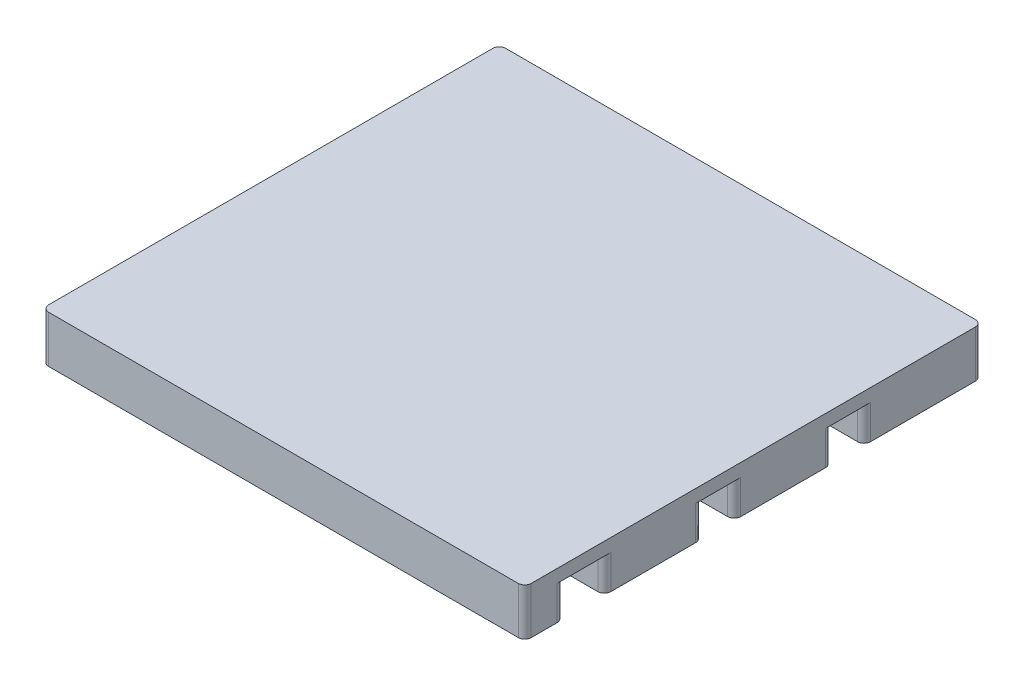
SolidWorks part; units mm, degrees
ref_plane "Front Plane" through (0, 0, 0) normal (0, 0, 1) x (1, 0, 0)
ref_plane "Top Plane" through (0, 0, 0) normal (0, 1, 0) x (1, 0, 0)
ref_plane "Right Plane" through (0, 0, 0) normal (1, 0, 0) x (0, 0, -1)
sketch "Sketch3" plane through (0, 0, 0) normal (0, 1, 0) x (1, 0, 0)
  line L1 (0, 0) -> (149, 0)
  line L2 (0, 0) -> (0, -141.12)
  line L3 (0, -141.12) -> (149, -141.12)
  line L4 (149, 0) -> (149, -141.12)
  dimension "D1" = 141.12
  dimension "D2" = 149
extrude "Boss-Extrude1" add sketch "Sketch3" along normal blind 4
sketch "Sketch5" plane through (0, 4, 0) normal (0, 1, 0) x (1, 0, 0)
  line L0 (0, 0) -> (0, -141.12) construction
  line L1 (149, 0) -> (82, 0)
  line L2 (149, 0) -> (149, -36.35)
  line L3 (149, -36.35) -> (82, -36.35)
  line L4 (82, 0) -> (82, -36.35)
  line L5 (0, -8.7) -> (67, -8.7)
  line L6 (0, -8.7) -> (0, -38.9)
  line L7 (0, -38.9) -> (67, -38.9)
  line L8 (67, -8.7) -> (67, -38.9)
  line L9 (149, 0) -> (0, 0) construction
  line L10 (149, -141.12) -> (149, 0) construction
  line L11 (0, -48.8) -> (67, -48.8)
  line L12 (0, -48.8) -> (0, -79)
  line L13 (0, -79) -> (67, -79)
  line L14 (67, -48.8) -> (67, -79)
  line L15 (0, -88.9) -> (67, -88.9)
  line L16 (0, -88.9) -> (0, -119.1)
  line L17 (0, -119.1) -> (67, -119.1)
  line L18 (67, -88.9) -> (67, -119.1)
  line L19 (149, -46.25) -> (82, -46.25)
  line L20 (149, -46.25) -> (149, -76.45)
  line L21 (149, -76.45) -> (82, -76.45)
  line L22 (82, -46.25) -> (82, -76.45)
  line L23 (13, -8.7) -> (13, -21.7) construction
  line L24 (149, -86.35) -> (82, -86.35)
  line L25 (149, -86.35) -> (149, -116.55)
  line L26 (149, -116.55) -> (82, -116.55)
  line L27 (82, -86.35) -> (82, -116.55)
  line L28 (13, -21.7) -> (13, -27.9) construction
  line L29 (13, -27.9) -> (13, -38.9) construction
  line L30 (13, -21.7) -> (41, -21.7)
  line L31 (13, -27.9) -> (41, -27.9)
  line L32 (13, -48.8) -> (13, -61.8) construction
  line L33 (13, -61.8) -> (13, -68) construction
  line L34 (13, -68) -> (13, -79) construction
  line L35 (13, -61.8) -> (41, -61.8)
  line L36 (13, -68) -> (41, -68)
  line L37 (97, -36.35) -> (97, -25.35) construction
  line L38 (97, -25.35) -> (97, -19.15) construction
  line L39 (97, -19.15) -> (97, 0) construction
  line L40 (97, -19.15) -> (125, -19.15)
  line L41 (97, -25.35) -> (125, -25.35)
  line L42 (97, -46.25) -> (97, -59.25) construction
  line L43 (97, -59.25) -> (97, -65.45) construction
  line L44 (97, -65.45) -> (97, -76.45) construction
  line L45 (97, -59.25) -> (125, -59.25)
  line L46 (97, -65.45) -> (125, -65.45)
  line L47 (13, -88.9) -> (13, -101.9) construction
  line L48 (13, -101.9) -> (13, -108.1) construction
  line L49 (13, -108.1) -> (13, -119.1) construction
  line L50 (13, -101.9) -> (41, -101.9)
  line L51 (13, -108.1) -> (41, -108.1)
  line L52 (97, -86.35) -> (97, -99.35) construction
  line L53 (97, -99.35) -> (97, -105.55) construction
  line L54 (97, -105.55) -> (97, -116.55) construction
  line L55 (97, -99.35) -> (125, -99.35)
  line L56 (97, -105.55) -> (125, -105.55)
  arc A0 (13, -27.9) -> (13, -21.7) centre (13, -24.8) cw
  arc A1 (41, -21.7) -> (41, -27.9) centre (41, -24.8) cw
  arc A2 (13, -61.8) -> (13, -68) centre (13, -64.9) ccw
  arc A3 (41, -61.8) -> (41, -68) centre (41, -64.9) cw
  arc A4 (97, -25.35) -> (97, -19.15) centre (97, -22.25) cw
  arc A5 (125, -19.15) -> (125, -25.35) centre (125, -22.25) cw
  arc A6 (97, -65.45) -> (97, -59.25) centre (97, -62.35) cw
  arc A7 (125, -59.25) -> (125, -65.45) centre (125, -62.35) cw
  arc A8 (13, -101.9) -> (13, -108.1) centre (13, -105) ccw
  arc A9 (41, -101.9) -> (41, -108.1) centre (41, -105) cw
  arc A10 (97, -99.35) -> (97, -105.55) centre (97, -102.45) ccw
  arc A11 (125, -99.35) -> (125, -105.55) centre (125, -102.45) cw
  point P85 (0, 0)
  point P86 (0, 0)
  line M18 (0, 0) -> (0, -141.12)
  line M20 (149, -141.12) -> (149, 0)
  line M21 (149, 0) -> (0, 0)
  dimension "D1" = 67
  dimension "D2" = 36.35
  dimension "D3" = 67
  dimension "D4" = 30.2
  dimension "D5" = 8.7
  dimension "D6" = 30.2
  dimension "D7" = 9.9
  dimension "D8" = 9.9
  dimension "D9" = 30.2
  dimension "D10" = 9.9
  dimension "D11" = 30.2
  dimension "D12" = 9.9
  dimension "D13" = 30.2
  dimension "D14" = 67
  dimension "D15" = 67
  dimension "D16" = 67
  dimension "D17" = 67
  dimension "D18" = 13
  dimension "D19" = 11
  dimension "D20" = 13
  dimension "D21" = 28
  dimension "D22" = 13
  dimension "D23" = 11
  dimension "D24" = 28
  dimension "D26" = 11
  dimension "D27" = 24
  dimension "D28" = 28
  dimension "D29" = 11
  dimension "D30" = 13
  dimension "D31" = 13
  dimension "D32" = 11
  dimension "D33" = 13
  dimension "D34" = 11
extrude "Boss-Extrude2" add sketch "Sketch5" against normal blind 14.5 contours L8 L5 L7 L30 A1 L31 A0 M18 | L4 L3 L40 A5 L41 A4 M21 M20 | L14 L11 L13 L35 A3 L36 A2 M18 | L19 L22 L21 L45 A7 L46 A6 M20 | L18 L15 L17 L50 A9 L51 A8 M18 | L24 L27 L26 L55 A11 L56 A10 M20 region at (115.9109, 4, 17.8029) region at (148.2651, 4, 101.45) region at (148.2651, 4, 61.35) region at (33.5, 4, 89.6349) region at (33.5, 4, 49.5349) region at (33.5, 4, 9.4349)
fillet "Fillet1" radius 2 24 edges at (149, -5.25, 86.35) (149, -5.25, 116.55) (82, -5.25, 116.55) (82, -5.25, 86.35) (67, -5.25, 88.9) (67, -5.25, 119.1) (0, -5.25, 119.1) (0, -5.25, 88.9) (0, -5.25, 79) (82, -5.25, 76.45) (149, -5.25, 76.45) (149, -5.25, 46.25) (82, -5.25, 46.25) (67, -5.25, 48.8) (67, -5.25, 79) (0, -5.25, 48.8) (0, -5.25, 38.9) (67, -5.25, 38.9) (82, -5.25, 36.35) (149, -5.25, 36.35) (149, -3.25, 0) (82, -5.25, 0) (67, -5.25, 8.7) (0, -5.25, 8.7)
sketch "Sketch6" plane through (0, 0, 0) normal (0, -1, 0) x (1, 0, 0)
  line L0 (0, 129.12) -> (149, 129.12)
  line L1 (0, 117.1) -> (0, 141.12) construction
  line L2 (149, 141.12) -> (149, 114.55) construction
  line L3 (149, 129.12) -> (149, 141.12)
  line L4 (149, 141.12) -> (0, 141.12)
  line L5 (0, 141.12) -> (0, 129.12)
  dimension "D1" = 12
extrude "Boss-Extrude3" add sketch "Sketch6" along normal blind 10.5
fillet "Fillet2" radius 2 5 edges at (149, -5.25, 129.12) (0, -5.25, 129.12) (0, -3.25, 141.12) (149, -3.25, 141.12) (0, 2, 0)
